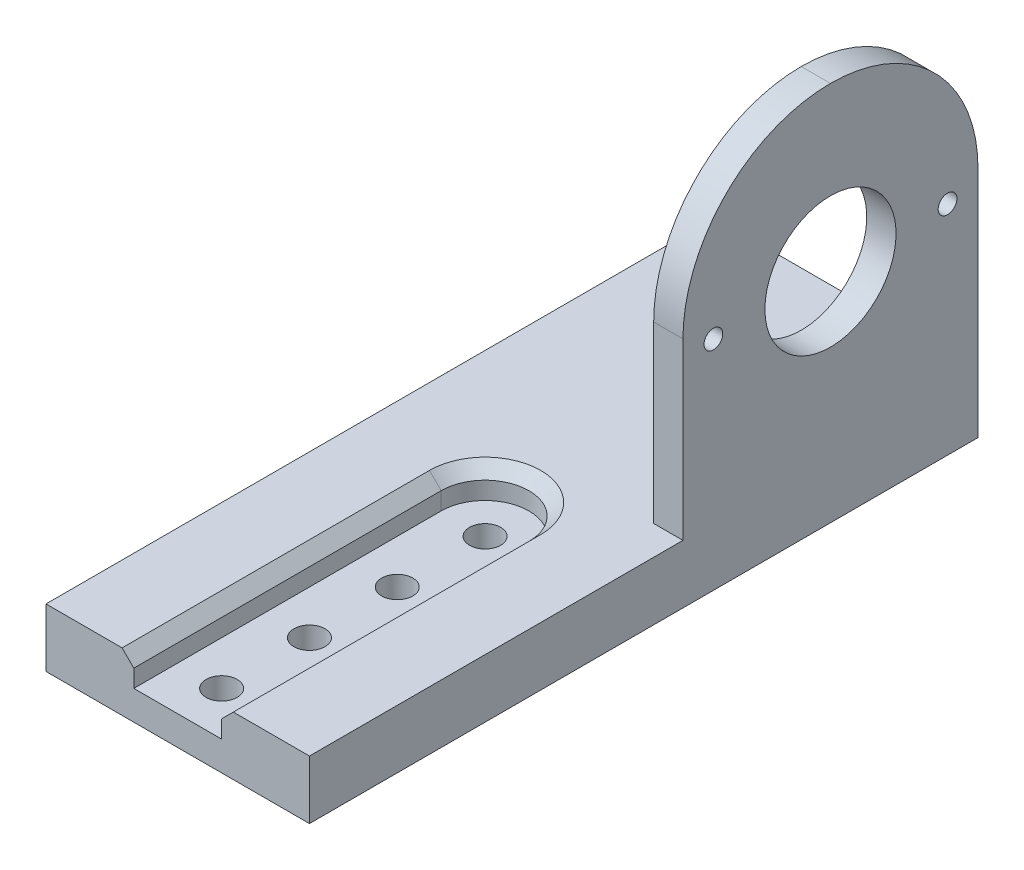
SolidWorks part; units mm, degrees
ref_plane "Front Plane" through (0, 0, 0) normal (0, 0, 1) x (1, 0, 0)
ref_plane "Top Plane" through (0, 0, 0) normal (0, 1, 0) x (1, 0, 0)
ref_plane "Right Plane" through (0, 0, 0) normal (1, 0, 0) x (0, 0, -1)
sketch "Sketch1" plane through (0, 0, 0) normal (0, 1, 0) x (1, 0, 0)
  line L1 (0, 0) -> (57.15, 0)
  line L2 (0, 0) -> (0, 145.034)
  line L3 (0, 145.034) -> (57.15, 145.034)
  line L4 (57.15, 0) -> (57.15, 145.034)
  dimension "D1" = 57.15
  dimension "D2" = 145.034
extrude "Boss-Extrude1" add sketch "Sketch1" along normal blind 12.7
sketch "Sketch4" plane through (0, 0, 0) normal (0, -1, 0) x (-1, 0, 0)
  line L0 (0, 0) -> (-57.15, 0) construction
  line L1 (-57.15, 0) -> (-57.15, 145.034) construction
  circle A0 centre (-28.575, 9.525) radius 3.3782
  circle A1 centre (-28.575, 28.575) radius 3.3782
  circle A2 centre (-28.575, 47.625) radius 3.3782
  circle A3 centre (-28.575, 66.675) radius 3.3782
  dimension "D1" = 6.7564
  dimension "D2" = 6.7564
  dimension "D3" = 6.7564
  dimension "D4" = 6.7564
  dimension "D5" = 19.05
  dimension "D6" = 19.05
  dimension "D7" = 19.05
  dimension "D8" = 9.525
  dimension "D9" = 28.575
  dimension "D10" = 28.575
  dimension "D11" = 28.575
  dimension "D12" = 28.575
extrude "Cut-Extrude3" cut sketch "Sketch4" against normal through all
sketch "Sketch7" plane through (0, 0, 0) normal (0, -1, 0) x (1, 0, 0)
  line L0 (57.15, 0) -> (57.15, -145.034) construction
  line L1 (57.15, -81.026) -> (50.8, -81.026)
  line L2 (57.15, -81.026) -> (57.15, -145.034)
  line L3 (57.15, -145.034) -> (50.8, -145.034)
  line L4 (50.8, -81.026) -> (50.8, -145.034)
  line L8 (57.15, -145.034) -> (0, -145.034) construction
  dimension "D1" = 6.35
  dimension "D2" = 64.008
  dimension "D3" = 0
sketch "Sketch8" plane through (0, 12.7, 0) normal (0, 1, 0) x (1, 0, 0)
  line L0 (19.05, 66.675) -> (19.05, 0)
  line L1 (0, 0) -> (57.15, 0) construction
  line L2 (19.05, 0) -> (38.1, 0)
  line L3 (38.1, 0) -> (38.1, 66.675)
  line L4 (0, 145.034) -> (0, 0) construction
  line L5 (57.15, 0) -> (57.15, 145.034) construction
  arc A4 (38.1, 66.675) -> (19.05, 66.675) centre (28.575, 66.675) ccw
  dimension "D1" = 19.05
  dimension "D2" = 19.05
  dimension "D3" = 9.525
  dimension "D4" = 66.675
extrude "Cut-Extrude4" cut sketch "Sketch8" against normal blind 6.35
chamfer "Chamfer1" distance 2.54 angle 45 3 edges at (19.05, 12.7, -33.3375) (28.575, 12.7, -76.2) (38.1, 12.7, -33.3375)
extrude "Boss-Extrude2" add sketch "Sketch7" against normal blind 82.55
sketch "Sketch9" plane through (50.8, 0, 0) normal (-1, 0, 0) x (0, 0, 1)
  line L0 (-145.034, 82.55) -> (-145.034, 12.7) construction
  line L1 (-81.026, 82.55) -> (-145.034, 82.55) construction
  line L2 (-81.026, 82.55) -> (-81.026, 12.7) construction
  circle A0 centre (-113.03, 47.2173) radius 14.224
  circle A1 centre (-87.63, 47.2173) radius 2.032
  circle A2 centre (-138.43, 47.2173) radius 2.032
  dimension "D1" = 28.448
  dimension "D7" = 4.064
  dimension "D8" = 4.064
  dimension "D2" = 25.4
  dimension "D3" = 25.4
  dimension "D4" = 6.604
  dimension "D5" = 35.3327
  dimension "D6" = 6.604
  dimension "D9" = 35.3327
extrude "Cut-Extrude5" cut sketch "Sketch9" against normal blind 82.55
fillet "Fillet1" radius 32.004 2 edges at (53.975, 82.55, -81.026) (53.975, 82.55, -145.034)
